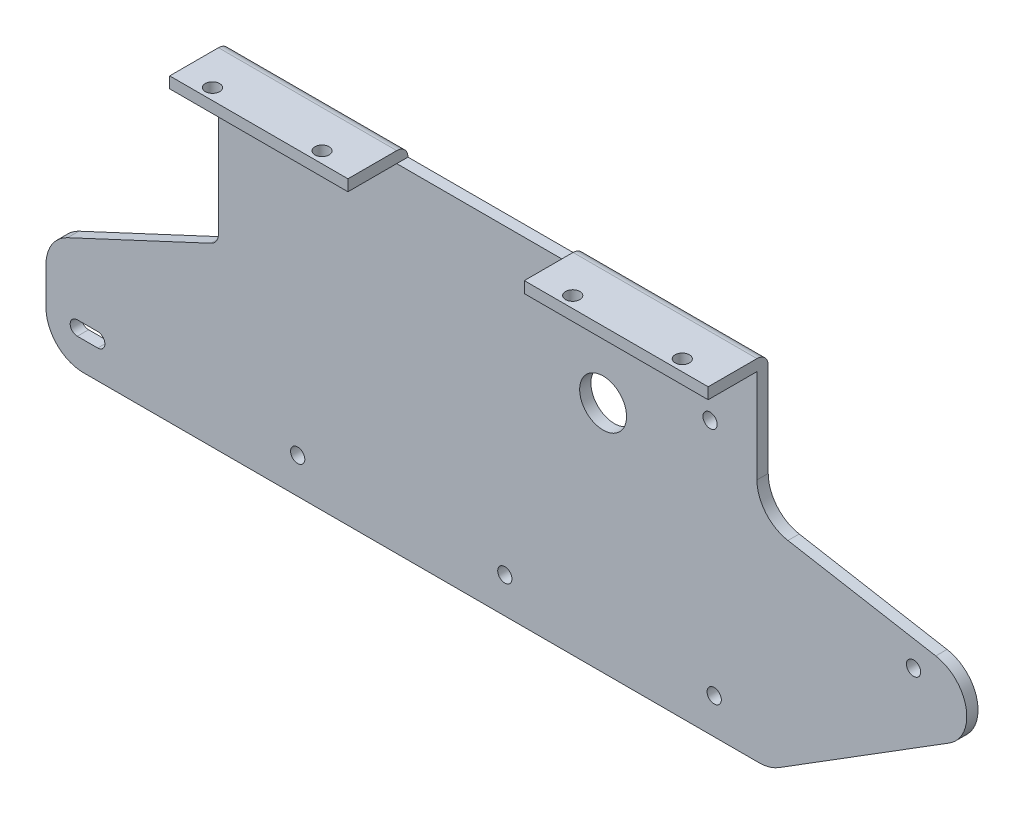
SolidWorks part; units mm, degrees
material "1060 Alloy"
ref_plane "Front Plane" through (0, 0, 0) normal (0, 0, 1) x (1, 0, 0)
ref_plane "Top Plane" through (0, 0, 0) normal (0, 1, 0) x (1, 0, 0)
ref_plane "Right Plane" through (0, 0, 0) normal (1, 0, 0) x (0, 0, -1)
sketch "Sketch1" plane through (0, 0, 0) normal (0, 0, 1) x (1, 0, 0)
  line L0 (0, 0) -> (143.5, 0)
  line L1 (143.5, 0) -> (143.5, -25)
  line L2 (151.7635, -34.8481) -> (191.1558, -41.794)
  line L3 (194.7185, -60.1226) -> (149.3364, -88.4805)
  line L4 (144.0372, -90) -> (-35.9628, -90)
  line L5 (-45.9628, -80) -> (-45.9628, -70)
  line L6 (-40.189, -60.9369) -> (-1.9907, -43.1248)
  line L7 (0, 0) -> (0, -40)
  arc A0 (-45.9628, -70) -> (-40.189, -60.9369) centre (-35.9628, -70) cw
  arc A1 (143.5, -25) -> (151.7635, -34.8481) centre (153.5, -25) ccw
  arc A2 (191.1558, -41.794) -> (194.7185, -60.1226) centre (189.4193, -51.6421) cw
  arc A3 (144.0372, -90) -> (149.3364, -88.4805) centre (144.0372, -80) ccw
  arc A4 (-45.9628, -80) -> (-35.9628, -90) centre (-35.9628, -80) ccw
  arc A5 (-1.9907, -43.1248) -> (0, -40) centre (-3.4478, -40) ccw
  dimension "D6" = 10
  dimension "D7" = 10
  dimension "D10" = 10
  dimension "D11" = 40
  dimension "D12" = 10
  dimension "D15" = 10
  dimension "D1" = 143.5
  dimension "D2" = 25
  dimension "D3" = 40
  dimension "D4" = 90
  dimension "D5" = 10
  dimension "D8" = 180
  dimension "D9" = 32
  dimension "D13" = 10
  dimension "D14" = 25
extrude "Boss-Extrude1" add sketch "Sketch1" along normal blind 3
sketch "Sketch2" plane through (0, 0, 3) normal (0, 0, 1) x (1, 0, 0)
  line L0 (-35.9628, -90) -> (144.0372, -90) construction
  line L3 (149.3364, -88.4805) -> (194.7185, -60.1226) construction
  line L4 (132.1078, -80.5) -> (132.1078, -90) construction
  line L5 (-35.9628, -90) -> (144.0372, -90) construction
  line L6 (132.1078, -80.5) -> (162.1078, -80.5) construction
  line L7 (132.1078, -80.5) -> (76.3078, -80.5) construction
  line L9 (21.1078, -80.5) -> (-32.1672, -80.5) construction
  line L10 (-32.1672, -80.5) -> (-37.6172, -80.5) construction
  line L11 (-32.1672, -82.4) -> (-37.6172, -82.4)
  line L12 (-32.1672, -78.6) -> (-37.6172, -78.6)
  line L13 (102.5, -27.75) -> (0, -27.75) construction
  line L14 (0, 0) -> (0, -40) construction
  line L15 (143.5, 0) -> (0, 0) construction
  circle A0 centre (185.2283, -47.5688) radius 1.9
  circle A2 centre (132.1078, -80.5) radius 1.9
  circle A3 centre (76.3078, -80.5) radius 1.9
  circle A4 centre (21.1078, -80.5) radius 1.9
  arc A5 (-32.1672, -82.4) -> (-32.1672, -78.6) centre (-32.1672, -80.5) ccw
  arc A6 (-37.6172, -78.6) -> (-37.6172, -82.4) centre (-37.6172, -80.5) ccw
  circle A7 centre (102.5, -27.75) radius 6.25
  circle A8 centre (131.0078, -17.5) radius 1.9
  point P3 (188.37, -53.2821)
  point P22 (-34.8922, -80.5)
  dimension "D1" = 3.8
  dimension "D7" = 1.9
  dimension "D8" = 5.45
  dimension "D11" = 12.5
  dimension "D2" = 62
  dimension "D3" = 9.5
  dimension "D4" = 30
  dimension "D5" = 55.8
  dimension "D6" = 167
  dimension "D9" = 102.5
  dimension "D10" = 27.75
  dimension "D12" = 62.5
  dimension "D13" = 111
  dimension "D14" = 1.1
  dimension "D15" = 72.5
extrude "Cut-Extrude1" cut sketch "Sketch2" against normal through all contours A7 | A2 | A0 | A3 | A4 | L12 A6 L11 A5 | A8
sketch "Sketch3" plane through (143.5, 0, 0) normal (1, 0, 0) x (0, 0, -1)
  line L0 (0, 0) -> (-16, 0)
  line L1 (-3, 3) -> (-16, 3)
  line L2 (-16, 3) -> (-16, 0)
  line L3 (-3, 0) -> (0, 0)
  line L4 (-3, -25) -> (-3, 0) construction
  line L5 (-3, -25) -> (-3, 0)
  line L6 (0, -25) -> (0, 0) construction
  line L7 (0, -25) -> (0, 0)
  arc A2 (-3, 3) -> (0, 0) centre (-3, 0) cw
  line M10 (0, 0) -> (-3, 0)
  dimension "D1" = 3
  dimension "D2" = 16
extrude "Boss-Extrude3" add sketch "Sketch3" against normal up to surface (143.5 mm away) contours A2 L1 L2 L0 M10 region at (143.5, 1.4652, 8.3073) up to face at (0, -20, 1.5)
sketch "Sketch6" plane through (0, 3, 0) normal (0, 1, 0) x (1, 0, 0)
  line L0 (47.5, 0) -> (94.5, 0)
  line L1 (143.5, 0) -> (0, 0) construction
  line L2 (94.5, 0) -> (94.5, -16)
  line L3 (0, -16) -> (143.5, -16) construction
  line L4 (94.5, -16) -> (47.5, -16)
  line L5 (47.5, -16) -> (47.5, 0)
  line L6 (0, -16) -> (0, -3) construction
  line L7 (143.5, -3) -> (143.5, -16) construction
  dimension "D1" = 47.5
  dimension "D2" = 49
extrude "Cut-Extrude4" cut sketch "Sketch6" against normal up to vertex (3 mm away) up to point (143.5, 0, 3)
sketch "Sketch7" plane through (0, 3, 0) normal (0, 1, 0) x (1, 0, 0)
  line L0 (0, -13) -> (143.5, -13) construction
  line L1 (0, -16) -> (0, -3) construction
  line L2 (143.5, -3) -> (143.5, -16) construction
  line L3 (0, -16) -> (47.5, -16) construction
  line L4 (94.5, -16) -> (94.5, -3) construction
  line L5 (47.5, -3) -> (47.5, -16) construction
  circle A0 centre (133.6, -13) radius 1.9
  circle A1 centre (104.4, -13) radius 1.9
  circle A2 centre (37.6, -13) radius 1.9
  circle A3 centre (8.4, -13) radius 1.9
  dimension "D6" = 3.8
  dimension "D1" = 3
  dimension "D2" = 9.9
  dimension "D3" = 9.9
  dimension "D4" = 9.9
  dimension "D5" = 8.4
extrude "Cut-Extrude5" cut sketch "Sketch7" against normal through all
